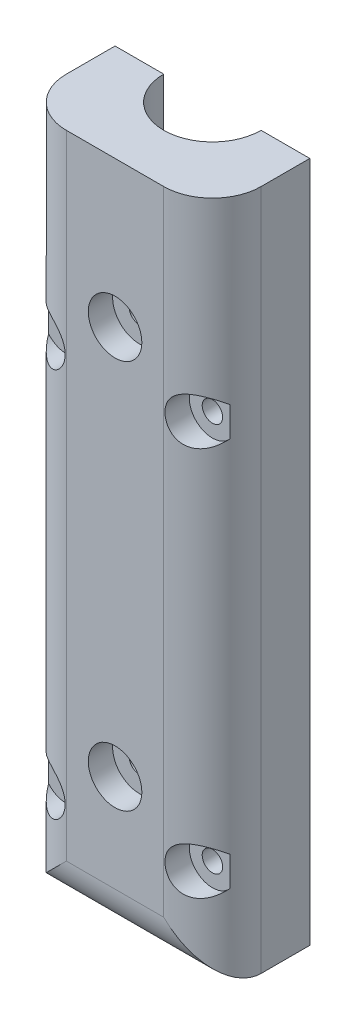
SolidWorks part; units mm, degrees
ref_plane "Front Plane" through (0, 0, 0) normal (0, 0, 1) x (1, 0, 0)
ref_plane "Top Plane" through (0, 0, 0) normal (0, 1, 0) x (1, 0, 0)
ref_plane "Right Plane" through (0, 0, 0) normal (1, 0, 0) x (0, 0, -1)
sketch "Sketch3" plane through (0, 0, 0) normal (0, 0, 1) x (1, 0, 0)
  line L1 (-20, -70) -> (20, -70)
  line L2 (-20, -70) -> (-20, 70)
  line L3 (-20, 70) -> (20, 70)
  line L4 (20, -70) -> (20, 70)
  line L5 (0, 70) -> (0, -70) construction
  line L6 (-20, 0) -> (20, 0) construction
  point P0 (0, 0)
  dimension "D1" = 40
  dimension "D2" = 140
extrude "Boss-Extrude1" add sketch "Sketch3" along normal blind 20
sketch "Sketch4" plane through (0, 70, 0) normal (0, 1, 0) x (1, 0, 0)
  line L0 (20, 0) -> (-20, 0) construction
  circle A0 centre (0, 0) radius 10
  dimension "D1" = 20
extrude "Cut-Extrude1" cut sketch "Sketch4" against normal through all
sketch "Sketch6" plane through (0, 0, 20) normal (0, 0, 1) x (1, 0, 0)
  line L0 (0, 0) -> (0, 40) construction
  line L1 (0, 0) -> (0, -40) construction
  line L2 (20, 70) -> (-20, 70) construction
  line L3 (-15, 70) -> (-15, -70) construction
  line L4 (-20, -70) -> (20, -70) construction
  line L5 (15, -70) -> (15, 70) construction
  circle A0 centre (0, 40) radius 2.1
  circle A1 centre (0, -40) radius 2.1
  circle A2 centre (0, 40) radius 5.5
  circle A3 centre (0, -40) radius 5.5
  circle A4 centre (-15, 30) radius 2.1
  circle A5 centre (-15, 30) radius 4.75
  circle A6 centre (-15, -50) radius 2.1
  circle A7 centre (-15, -50) radius 4.75
  circle A8 centre (15, -50) radius 4.75
  circle A9 centre (15, -50) radius 2.1
  circle A10 centre (15, 30) radius 4.75
  circle A11 centre (15, 30) radius 2.1
  dimension "D1" = 11
  dimension "D2" = 11
  dimension "D3" = 4.2
  dimension "D4" = 4.2
  dimension "D7" = 4.2
  dimension "D11" = 9.5
  dimension "D12" = 4.2
  dimension "D13" = 9.5
  dimension "D5" = 40
  dimension "D6" = 40
  dimension "D8" = 40
  dimension "D9" = 30
  dimension "D10" = 15
  dimension "D14" = 20
extrude "Cut-Extrude10" cut sketch "Sketch6" against normal blind 5
extrude "Cut-Extrude11" cut sketch "Sketch6<2>" against normal through all contours A4 | A0 | A11 | A6 | A1 | A9
sketch "Sketch6<2>" plane through (0, 0, 20) normal (0, 0, 1) x (1, 0, 0) same geometry as "Sketch6"
fillet "Fillet1" radius 10 3 edges at (0, -70, 20) (20, 0, 20) (-20, 0, 20)
